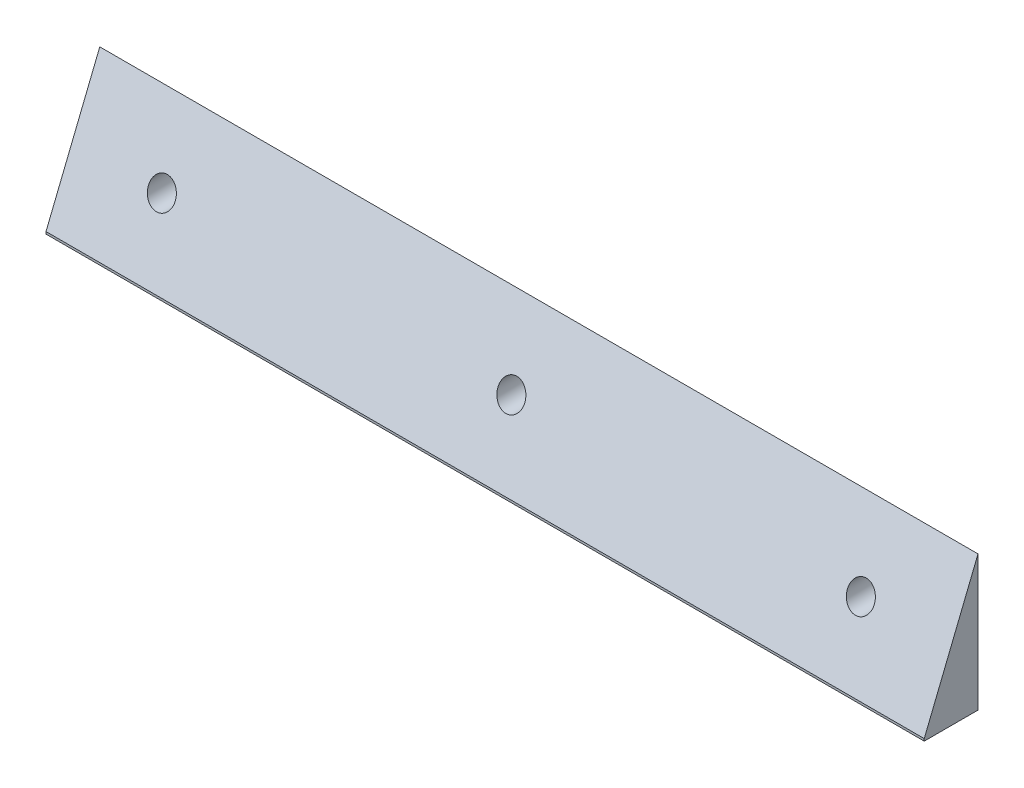
SolidWorks part; units mm, degrees
material "AISI 4340 Aço, normalizado"
ref_plane "Plano frontal" through (0, 0, 0) normal (0, 0, 1) x (1, 0, 0)
ref_plane "Plano superior" through (0, 0, 0) normal (0, 1, 0) x (1, 0, 0)
ref_plane "Plano direito" through (0, 0, 0) normal (1, 0, 0) x (0, 0, -1)
sketch "Esboço1" plane through (0, 0, 0) normal (0, 0, 1) x (1, 0, 0)
  line L1 (0, 0) -> (98, 0)
  line L2 (0, 0) -> (0, -25)
  line L3 (0, -25) -> (98, -25)
  line L4 (98, 0) -> (98, -25)
  dimension "D1" = 98
  dimension "D2" = 25
extrude "Ressalto-extrusão1" add sketch "Esboço1" along normal blind 6
chamfer "Chanfro1" distance 10 angle 68 1 edges at (49, 0, 6) first distance on face at (49, 0, 3)
sketch "Esboço3" plane through (0, 0, 0) normal (0, 0, -1) x (-1, 0, 0)
  line L0 (-98, -17.5) -> (0, -17.5) construction
  line L1 (-98, -25) -> (-98, -9.9003) construction
  line L2 (0, -9.9003) -> (0, -25) construction
  line L3 (0, -25) -> (-98, -25) construction
  circle A0 centre (-49, -17.5) radius 1.5
  circle A1 centre (-10, -17.5) radius 1.5
  circle A2 centre (-88, -17.5) radius 1.5
  dimension "D2" = 3
  dimension "D3" = 3
  dimension "D4" = 3
  dimension "D1" = 7.5
  dimension "D5" = 10
  dimension "D6" = 10
extrude "Corte-extrusão1" cut sketch "Esboço3" against normal blind 6
